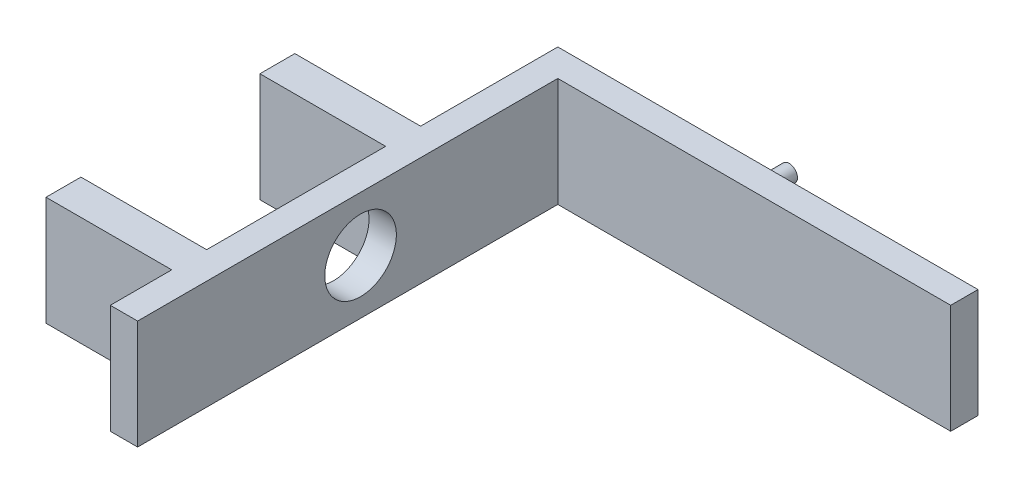
SolidWorks part; units mm, degrees
ref_plane "Front Plane" through (0, 0, 0) normal (0, 0, 1) x (1, 0, 0)
ref_plane "Top Plane" through (0, 0, 0) normal (0, 1, 0) x (1, 0, 0)
ref_plane "Right Plane" through (0, 0, 0) normal (1, 0, 0) x (0, 0, -1)
sketch "Sketch1" plane through (0, 0, 0) normal (0, 1, 0) x (1, 0, 0)
  line L1 (-2.7577, -19.8611) -> (1.211, -19.8611)
  line L2 (-2.7577, -19.8611) -> (-2.7577, 45.2264)
  line L3 (-2.7577, 45.2264) -> (6.2797, 45.2264)
  line L4 (1.211, -19.8611) -> (1.211, 41.2577)
  line L5 (-2.7577, -19.8611) -> (6.2797, 45.2264) construction
  line L6 (-2.7577, 45.2264) -> (1.211, -19.8611) construction
  line L7 (6.2797, 45.2264) -> (58.361, 45.2264)
  line L9 (1.211, 41.2577) -> (58.361, 41.2577)
  line L10 (58.361, 45.2264) -> (58.361, 41.2577)
  point P0 (0, 0)
  dimension "D1" = 3.9688
  dimension "D2" = 3.9688
  dimension "D3" = 57.15
  dimension "D4" = 61.1187
extrude "Boss-Extrude1" add sketch "Sketch1" along normal mid plane 15.875
sketch "Sketch3" plane through (-2.7577, 0, 0) normal (-1, 0, 0) x (0, 0, 1)
  circle A0 centre (-12.5666, 0) radius 5.207
  dimension "D1" = 10.414
extrude "Cut-Extrude1" cut sketch "Sketch3" against normal up to surface (3.9688 mm away) up to face at (1.211, 0, -10.6983)
sketch "Sketch4" plane through (0, 0, -45.2264) normal (0, 0, -1) x (-1, 0, 0)
  line L0 (-58.361, 7.9375) -> (-58.361, -7.9375) construction
  circle A0 centre (-22.0073, 0) radius 1.2065
  dimension "D1" = 2.413
  dimension "D2" = 36.3537
extrude "Boss-Extrude2" add sketch "Sketch4" along normal blind 8.89
sketch "Sketch5" plane through (-2.7577, 0, 0) normal (-1, 0, 0) x (0, 0, 1)
  line L0 (-45.2264, 7.9375) -> (19.8611, 7.9375) construction
  line L1 (-25.2666, -7.9375) -> (-20.1866, -7.9375)
  line L2 (-25.2666, -7.9375) -> (-25.2666, 7.9375)
  line L3 (-25.2666, 7.9375) -> (-20.1866, 7.9375)
  line L4 (-20.1866, -7.9375) -> (-20.1866, 7.9375)
  line L5 (-25.2666, -7.9375) -> (-20.1866, 7.9375) construction
  line L6 (-25.2666, 7.9375) -> (-20.1866, -7.9375) construction
  line L7 (-45.2264, -7.9375) -> (19.8611, -7.9375) construction
  line L9 (10.9284, 7.9375) -> (5.8484, 7.9375)
  line L10 (10.9284, 7.9375) -> (10.9284, -7.9375)
  line L11 (10.9284, -7.9375) -> (5.8484, -7.9375)
  line L12 (5.8484, 7.9375) -> (5.8484, -7.9375)
  circle A1 centre (-12.5666, 0) radius 5.207 construction
  point P0 (-22.7266, 0)
  dimension "D3" = 18.415
  dimension "D1" = 7.62
  dimension "D2" = 5.08
  dimension "D4" = 5.08
extrude "Boss-Extrude3" add sketch "Sketch5" along normal blind 18.288
